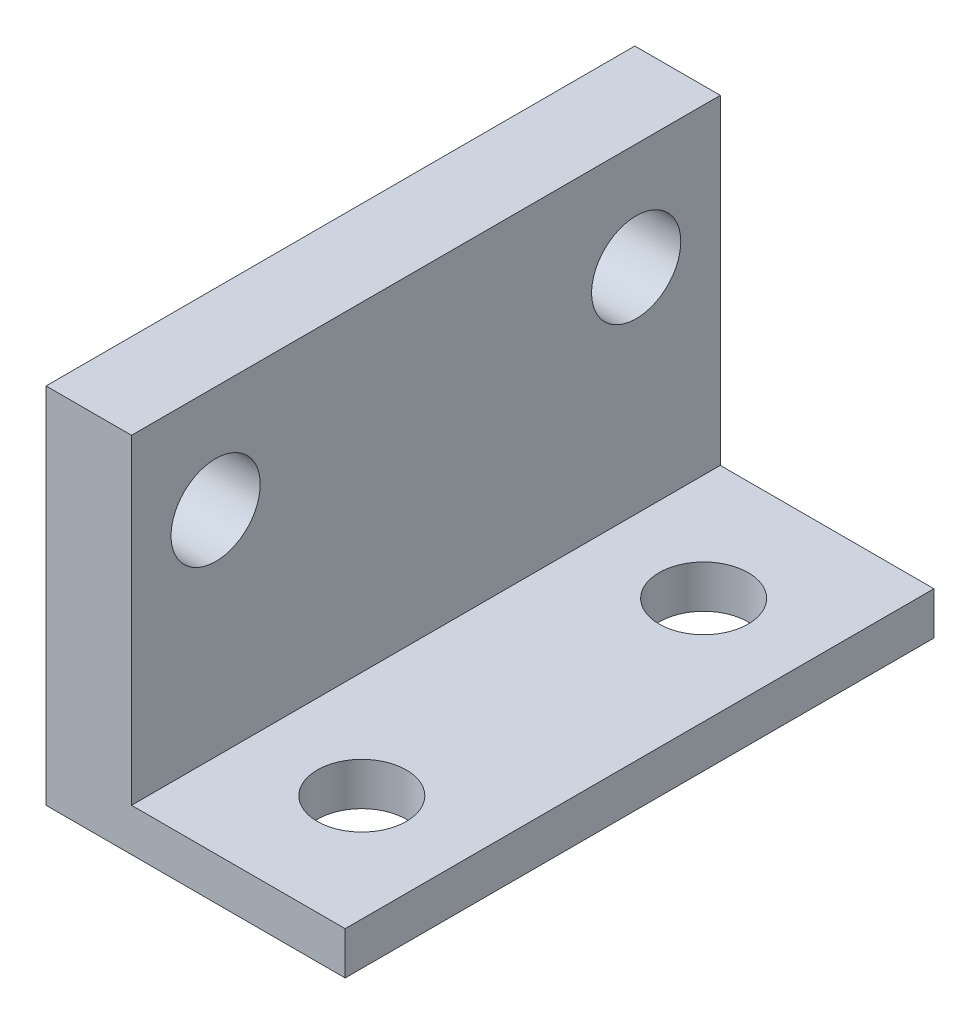
SolidWorks part; units mm, degrees
ref_plane "Front Plane" through (0, 0, 0) normal (0, 0, 1) x (1, 0, 0)
ref_plane "Top Plane" through (0, 0, 0) normal (0, 1, 0) x (1, 0, 0)
ref_plane "Right Plane" through (0, 0, 0) normal (1, 0, 0) x (0, 0, -1)
sketch "Sketch1" plane through (0, 0, 0) normal (0, 0, 1) x (1, 0, 0)
  line L1 (0, 0) -> (17.78, 0)
  line L2 (0, 0) -> (0, 2.54)
  line L3 (0, 2.54) -> (17.78, 2.54)
  line L4 (17.78, 0) -> (17.78, 2.54)
  line L5 (0, 2.54) -> (5.08, 2.54)
  line L6 (0, 2.54) -> (0, 21.59)
  line L7 (0, 21.59) -> (5.08, 21.59)
  line L8 (5.08, 2.54) -> (5.08, 21.59)
  dimension "D1" = 5.08
  dimension "D2" = 12.7
  dimension "D3" = 19.05
  dimension "D4" = 2.54
extrude "Boss-Extrude1" add sketch "Sketch1" along normal blind 35 contours L6 L5 L8 L7 | L2 L1 L4 L3
hole_wizard "Ø5.0mm Dowel Hole1" positions "Sketch2" profile "Sketch3" hole size "Ø5.0" standard "ANSI Metric" end condition through all
sketch "Sketch2" plane through (5.08, 0, 0) normal (1, 0, 0) x (0, 0, -1)
  line L4 (-30, 15.24) -> (-5, 15.24) construction
  line L6 (-35, 0) -> (0, 0) construction
  point P0 (-30, 15.24)
  point P2 (-5, 15.24)
  point P19 (-17.5, 0)
  point P20 (-17.5, 15.24)
  dimension "D1" = 25
  dimension "D2" = 15.24
sketch "Sketch3" plane through (5.08, 15.24, 30) normal (0, 1, 0) x (0, 0, -1)
  line L0 (0, 0) -> (0, 5.08)
  line L1 (0, 5.08) -> (2.65, 5.08)
  line L2 (2.65, 5.08) -> (2.65, 0)
  line L5 (2.65, 0) -> (0, 0)
  line L11 (0, -6.35) -> (0, 107.95) construction
  dimension "Thru Hole Dia." = 5.3
  dimension "Thru Hole Depth" = 5.08
hole_wizard "Ø5.0mm Dowel Hole2" positions "Sketch4" profile "Sketch5" hole size "Ø5.0" standard "ANSI Metric" end condition through all
sketch "Sketch4" plane through (0, 2.54, 0) normal (0, 1, 0) x (1, 0, 0)
  line L2 (11.43, -7.34) -> (11.43, -27.66) construction
  line L3 (17.78, -35) -> (17.78, 0) construction
  line L6 (0, -35) -> (0, 0) construction
  point P0 (11.43, -27.66)
  point P2 (11.43, -7.34)
  point P16 (17.78, -17.5)
  point P17 (11.43, -17.5)
  dimension "D1" = 20.32
  dimension "D2" = 11.43
sketch "Sketch5" plane through (11.43, 2.54, 27.66) normal (1, 0, 0) x (0, 0, 1)
  line L0 (0, 0) -> (0, 2.54)
  line L1 (0, 2.54) -> (2.65, 2.54)
  line L2 (2.65, 2.54) -> (2.65, 0)
  line L5 (2.65, 0) -> (0, 0)
  line L11 (0, -6.35) -> (0, 107.95) construction
  dimension "Thru Hole Dia." = 5.3
  dimension "Thru Hole Depth" = 2.54
equation "\"wall thicc\"= 2.5mm"
equation "\"press fit\"= 0.3mm"
equation "\"shaft thick\"= 5mm + \"press fit\""
equation "\"D4@Sketch1\"=\"wall thicc\""
